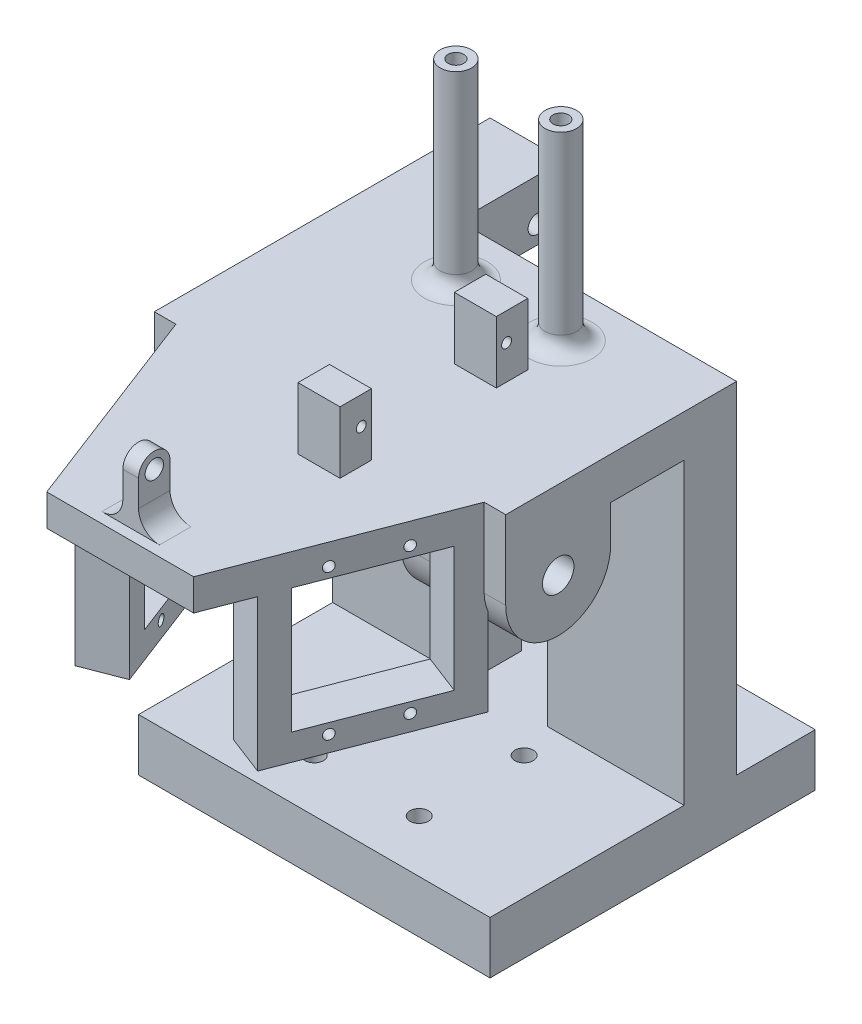
SolidWorks part; units mm, degrees
ref_plane "前视基准面" through (0, 0, 0) normal (0, 0, 1) x (1, 0, 0)
ref_plane "上视基准面" through (0, 0, 0) normal (0, 1, 0) x (1, 0, 0)
ref_plane "右视基准面" through (0, 0, 0) normal (1, 0, 0) x (0, 0, -1)
sketch "草图1" plane through (0, 0, 0) normal (0, 1, 0) x (1, 0, 0)
  line L1 (-33.5, 31) -> (33.5, 31)
  line L2 (-33.5, 31) -> (-33.5, -31)
  line L3 (-33.5, -31) -> (33.5, -31)
  line L4 (33.5, 31) -> (33.5, -31)
  line L5 (-33.5, 31) -> (33.5, -31) construction
  line L6 (-33.5, -31) -> (33.5, 31) construction
  point P0 (0, 0)
  dimension "D1" = 62
  dimension "D2" = 67
extrude "凸台-拉伸1" add sketch "草图1" along normal blind 10
sketch "草图3" plane through (0, 10, 0) normal (0, 1, 0) x (1, 0, 0)
  line L0 (-33.5, 31) -> (-33.5, -31) construction
  line L1 (-33.5, 36) -> (-19.5, 36)
  line L2 (-33.5, 36) -> (-33.5, 16)
  line L3 (-33.5, 16) -> (-19.5, 16)
  line L4 (-19.5, 36) -> (-19.5, 16)
  line L5 (33.5, 31) -> (-33.5, 31) construction
  dimension "D1" = 20
  dimension "D2" = 5
  dimension "D3" = 19.5
extrude "凸台-拉伸2" add sketch "草图3" along normal blind 12.5
sketch "草图4" plane through (-33.5, 0, 0) normal (-1, 0, 0) x (0, 0, 1)
  line L1 (-16, 10) -> (-6, 10)
  line L2 (-16, 10) -> (-16, 75)
  line L3 (-16, 75) -> (-6, 75)
  line L4 (-6, 10) -> (-6, 75)
  dimension "D1" = 10
  dimension "D2" = 65
extrude "凸台-拉伸3" add sketch "草图4" against normal blind 67
sketch "草图5" plane through (0, 75, 0) normal (0, 1, 0) x (1, 0, 0)
  line L0 (33.5, -31) -> (33.5, 6) construction
  line L1 (-33.5, 16) -> (33.5, 16)
  line L2 (-33.5, 16) -> (-33.5, -28)
  line L3 (-33.5, -28) -> (33.5, -28)
  line L4 (33.5, 16) -> (33.5, -28)
  dimension "D1" = 44
extrude "凸台-拉伸4" add sketch "草图5" against normal blind 8
sketch "草图6" plane through (33.5, 0, 0) normal (1, 0, 0) x (0, 0, -1)
  line L0 (6, 10) -> (6, 67) construction
  line L1 (-28, 75) -> (16, 75) construction
  line L2 (-28, 60) -> (-28, 67)
  line L3 (-28, 67) -> (6, 67) construction
  line L5 (-28, 67) -> (-8, 67)
  line L6 (-8, 67) -> (-8, 60)
  arc A0 (-28, 60) -> (-8, 60) centre (-18, 60) ccw
  dimension "D1" = 24
  dimension "D2" = 15
  dimension "D3" = 20
extrude "凸台-拉伸5" add sketch "草图6" against normal blind 20
sketch "草图7" plane through (33.5, 0, 0) normal (1, 0, 0) x (0, 0, -1)
  line L0 (-28, 60) -> (-28, 70.0002)
  line L1 (-28, 60) -> (-28, 75) construction
  line L2 (-28, 70.0002) -> (-8, 70.0002)
  line L3 (-8, 70.0002) -> (-8, 60)
  arc A0 (-28, 60) -> (-8, 60) centre (-18, 60) ccw construction
  arc A1 (-28, 60) -> (-8, 60) centre (-18, 60) ccw
extrude "切除-拉伸1" cut sketch "草图7" against normal blind 8 from offset 6 offset against normal yes
sketch "草图8" plane through (0, 75, 0) normal (0, 1, 0) x (1, 0, 0)
  line L0 (0, -68) -> (14, -68)
  line L2 (14, -68) -> (29.3853, -28)
  line L3 (29.3853, -28) -> (0, -28)
  line L4 (0, -28) -> (0, -68)
  line L5 (-33.5, -28) -> (33.5, -28) construction
  dimension "D1" = 14
  dimension "D2" = 40
extrude "凸台-拉伸6" add sketch "草图8" against normal blind 6
sketch "草图9" plane through (33.5, 0, 0) normal (1, 0, 0) x (0, 0, -1)
  circle A0 centre (-18, 60) radius 3
  dimension "D1" = 6
extrude "切除-拉伸2" cut sketch "草图9" against normal blind 23
sketch "草图10" plane through (34.98, 0, 13.4544) normal (0.9333, 0, 0.359) x (0.359, 0, -0.9333)
  line L1 (-44, 75) -> (-15, 75)
  line L4 (-15, 75) -> (-15, 40.2)
  line L5 (-15, 40.2) -> (-43, 40.2)
  line L9 (-44, 45.2) -> (-20, 45.2)
  line L10 (-20, 45.2) -> (-20, 69)
  line L11 (-20, 69) -> (-44, 69)
  line L12 (-58.4413, 75) -> (-15.5844, 75) construction
  line L14 (-44, 75) -> (-49, 75)
  line L15 (-58.4413, 75) -> (-15.5844, 75) construction
  line L16 (-44, 69) -> (-44, 45.2)
  line L17 (-43, 40.2) -> (-49, 40.2)
  line L18 (-49, 75) -> (-49, 40.2)
  dimension "D1" = 5
  dimension "D2" = 5
  dimension "D3" = 29
  dimension "D4" = 15
  dimension "D5" = 24
  dimension "D6" = 28
  dimension "D7" = 5
  dimension "D8" = 6
  dimension "D9" = 23.8
extrude "凸台-拉伸7" add sketch "草图10" against normal blind 8
sketch "草图12" plane through (0, 75, 0) normal (0, 1, 0) x (1, 0, 0)
  line L1 (-33.5, 36) -> (-19.5, 36)
  line L2 (-33.5, 36) -> (-33.5, 16)
  line L3 (-33.5, 16) -> (-19.5, 16)
  line L4 (-19.5, 36) -> (-19.5, 16)
extrude "凸台-拉伸8" add sketch "草图12" against normal blind 11.5
sketch "草图13" plane through (27.5133, 0, 10.5825) normal (-0.9333, 0, -0.359) x (-0.359, 0, 0.9333)
  line L0 (58.4413, 69) -> (49, 69) construction
  line L7 (20, 69) -> (20, 45.2) construction
  line L8 (20, 45.2) -> (44, 45.2) construction
  circle A0 centre (38.5, 70.95) radius 0.95
  circle A1 centre (26.5, 70.95) radius 0.95
  circle A2 centre (26.5, 43.25) radius 0.95
  circle A3 centre (38.5, 43.25) radius 0.95
  dimension "D2" = 6.5
  dimension "D3" = 1.95
  dimension "D4" = 1.95
  dimension "D5" = 12
  dimension "D6" = 1.9
  dimension "D7" = 1.9
  dimension "D13" = 1.9
  dimension "D14" = 1.9
extrude "切除-拉伸4" cut sketch "草图13" against normal up to surface (8 mm away) up to face at (22.5859, 60.64, 45.6776)
sketch "草图14" plane through (0, 75, 0) normal (0, 1, 0) x (1, 0, 0)
  line L0 (33.5, 6) -> (-33.5, 6) construction
  line L1 (3.7, -2) -> (11.7, -2)
  line L2 (3.7, -2) -> (3.7, -8)
  line L3 (3.7, -8) -> (11.7, -8)
  line L4 (11.7, -2) -> (11.7, -8)
  line L5 (11.7, -31.8) -> (11.7, -37.8)
  line L6 (3.7, -37.8) -> (11.7, -37.8)
  line L7 (3.7, -31.8) -> (3.7, -37.8)
  line L8 (3.7, -31.8) -> (11.7, -31.8)
  dimension "D1" = 11.7
  dimension "D2" = 3.7
  dimension "D3" = 6
  dimension "D4" = 14
  dimension "D5" = 6
  dimension "D6" = 8
  dimension "D7" = 23.8
extrude "凸台-拉伸9" add sketch "草图14" along normal blind 11.8
sketch "草图15" plane through (3.7, 0, 0) normal (-1, 0, 0) x (0, 0, 1)
  line L0 (8, 86.8) -> (8, 75) construction
  line L1 (28, 75) -> (-36, 75) construction
  line L2 (31.8, 75) -> (37.8, 75) construction
  line L3 (31.8, 86.8) -> (31.8, 75) construction
  circle A0 centre (33.75, 81.5) radius 0.95
  circle A1 centre (6.05, 81.5) radius 0.95
  dimension "D1" = 1.95
  dimension "D2" = 1.95
  dimension "D3" = 1.9
  dimension "D4" = 1.9
  dimension "D5" = 6.5
  dimension "D6" = 6.5
extrude "切除-拉伸5" cut sketch "草图15" against normal blind 11.8
sketch "草图16" plane through (0, 75, 0) normal (0, 1, 0) x (1, 0, 0)
  line L1 (-1.5, -60) -> (1.5, -60)
  line L2 (-1.5, -60) -> (-1.5, -66)
  line L3 (-1.5, -66) -> (1.5, -66)
  line L4 (1.5, -60) -> (1.5, -66)
  point P4 (0, -66)
  dimension "D2" = 6
  dimension "D3" = 3
  dimension "D4" = 60
extrude "凸台-拉伸10" add sketch "草图16" along normal blind 12
fillet "圆角1" 2 edges at (0, 87, 66) (0, 87, 60) type full round first side face at (0, 79.8, 66) second side face at (0, 79.8, 60) middle face at (0, 87, 63)
sketch "草图17" plane through (-1.5, 0, 0) normal (-1, 0, 0) x (0, 0, 1)
  circle A0 centre (63, 84) radius 1.75
  arc A1 (66, 84) -> (60, 84) centre (63, 84) ccw construction
  dimension "D1" = 3.5
extrude "切除-拉伸6" cut sketch "草图17" against normal blind 7
sketch "草图18" plane through (0, 75, 0) normal (0, 1, 0) x (1, 0, 0)
  line L0 (33.5, 16) -> (-19.5, 16) construction
  circle A0 centre (10, 6) radius 3
  dimension "D1" = 6
  dimension "D2" = 10
  dimension "D3" = 10
extrude "凸台-拉伸11" add sketch "草图18" along normal blind 36.5
fillet "圆角2" radius 3 1 edges at (10, 75, -3)
mirror "镜向1" about plane through (0, 0, 0) normal (1, 0, 0) of "圆角2", "凸台-拉伸11", "切除-拉伸4", "凸台-拉伸7", "切除-拉伸2", "凸台-拉伸6", "切除-拉伸1", "凸台-拉伸5"
sketch "草图20" plane through (-33.5, 0, 0) normal (-1, 0, 0) x (0, 0, 1)
  line L0 (-36, 63.5) -> (-16, 63.5) construction
  line L1 (-36, 63.5) -> (-36, 75) construction
  circle A0 centre (-31, 67) radius 1.75
  circle A1 centre (-21, 67) radius 1.75
  circle A2 centre (-31, 19) radius 1.75
  circle A3 centre (-21, 19) radius 1.75
  dimension "D1" = 3.5
  dimension "D2" = 10
  dimension "D3" = 48
  dimension "D4" = 3.5
  dimension "D5" = 5
extrude "切除-拉伸7" cut sketch "草图20" against normal blind 35
sketch "草图21" plane through (0, 0, -16) normal (0, 0, -1) x (-1, 0, 0)
  line L1 (-7.5, 65) -> (7.5, 65)
  line L2 (-7.5, 65) -> (-7.5, 10)
  line L3 (-7.5, 10) -> (7.5, 10)
  line L4 (7.5, 65) -> (7.5, 10)
  line L5 (-33.5, 10) -> (19.5, 10) construction
  point P8 (0, 10)
  dimension "D1" = 15
  dimension "D2" = 55
extrude "切除-拉伸8" cut sketch "草图21" against normal blind 35
sketch "草图24" plane through (0, 10, 0) normal (0, 1, 0) x (1, 0, 0)
  line L0 (-33.5, -31) -> (33.5, -31) construction
  circle A0 centre (-10, -21) radius 1.75
  circle A1 centre (10, -21) radius 1.75
  circle A2 centre (-10, -1) radius 1.75
  circle A3 centre (10, -1) radius 1.75
  point P10 (0, -31)
  dimension "D1" = 20
  dimension "D2" = 20
  dimension "D5" = 10
  dimension "D6" = 3.5
  dimension "D7" = 10
  dimension "D3" = 20
  dimension "D4" = 20
extrude "切除-拉伸11" cut sketch "草图24" against normal blind 18
sketch "草图25" plane through (0, 111.5, 0) normal (0, 1, 0) x (1, 0, 0)
  circle A0 centre (10, 6) radius 1.5
  circle A1 centre (-10, 6) radius 1.5
  dimension "D1" = 3
  dimension "D2" = 3
extrude "切除-拉伸12" cut sketch "草图25" against normal blind 10
fillet "圆角3" radius 4 2 edges at (-1.5, 75, 63) (1.5, 75, 63)
sketch "草图26" plane through (0, 69, 0) normal (0, -1, 0) x (1, 0, 0)
  line L0 (-14, 68) -> (14, 68) construction
  line L1 (-5.1, 64.3) -> (5.1, 64.3)
  line L2 (-5.1, 64.3) -> (-5.1, 60.6)
  line L3 (-5.1, 60.6) -> (5.1, 60.6)
  line L4 (5.1, 64.3) -> (5.1, 60.6)
  line L5 (-5.1, 64.3) -> (5.1, 60.6) construction
  line L6 (-5.1, 60.6) -> (5.1, 64.3) construction
  line L7 (-33.5, -31) -> (-33.5, 31) construction
  point P0 (0, 62.45)
  dimension "D1" = 10.2
  dimension "D2" = 3.7
  dimension "D3" = 3.7
  dimension "D4" = 28.4
extrude "凸台-拉伸12" add sketch "草图26" along normal blind 1
sketch "草图28" plane through (0, 68, 0) normal (0, -1, 0) x (1, 0, 0)
  line L0 (-33.5, -31) -> (-33.5, 31) construction
  line L1 (-14, 68) -> (14, 68) construction
  circle A0 centre (0, 62.5) radius 1.4
  point P2 (0, 0)
  point P3 (0, 0)
  point P8 (0.3097, 66.7018)
  dimension "D1" = 2.8
  dimension "D2" = 33.5
  dimension "D3" = 5.5
extrude "切除-拉伸13" cut sketch "草图28" against normal blind 1
